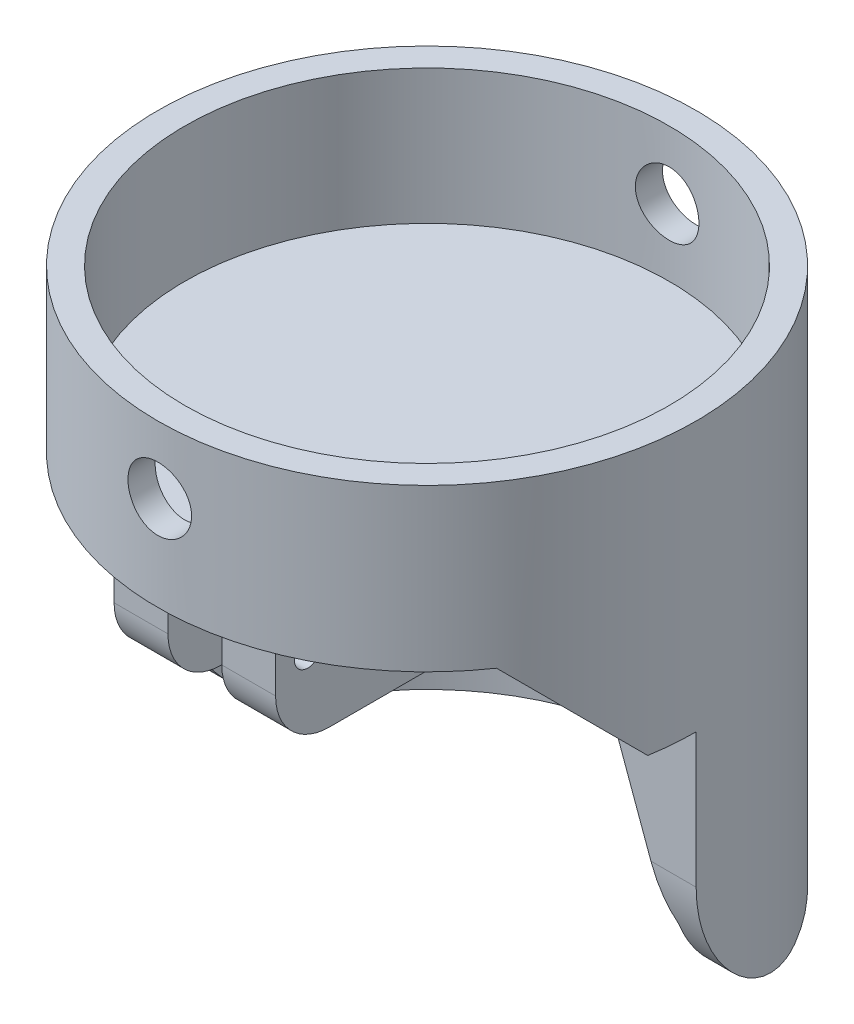
SolidWorks part; units mm, degrees
material "ABS"
ref_plane "Front Plane" through (0, 0, 0) normal (0, 0, 1) x (1, 0, 0)
ref_plane "Top Plane" through (0, 0, 0) normal (0, 1, 0) x (1, 0, 0)
ref_plane "Right Plane" through (0, 0, 0) normal (1, 0, 0) x (0, 0, -1)
sketch "Sketch2" plane through (0, 0, 0) normal (0, 1, 0) x (1, 0, 0)
  circle A0 centre (0, 0) radius 12.7
  dimension "D1" = 25.4
extrude "Boss-Extrude1" add sketch "Sketch2" along normal blind 12.7
sketch "Sketch3" plane through (0, 12.7, 0) normal (0, 1, 0) x (1, 0, 0)
  circle A0 centre (0, 0) radius 11.43
  dimension "D1" = 22.86
extrude "Cut-Extrude1" cut sketch "Sketch3" against normal blind 6.35
ref_plane "Plane1" through (0, 0, 12.7) normal (0, 0, 1) x (1, 0, 0)
sketch "Sketch4" plane through (0, 0, 12.7) normal (0, 0, 1) x (1, 0, 0)
  line L0 (0, 12.7) -> (0, 9.525)
  line L1 (12.7, 12.7) -> (-12.7, 12.7) construction
  circle A0 centre (0, 9.525) radius 1.5
  dimension "D2" = 3
  dimension "D1" = 3.175
extrude "Cut-Extrude2" cut sketch "Sketch4" against normal through all
sketch "Sketch5" plane through (0, 0, 0) normal (0, -1, 0) x (1, 0, 0)
  line L0 (-9.4733, 12.7) -> (9.4733, 12.7)
  line L1 (-9.4733, 12.7) -> (-9.4733, 8.4585)
  line L2 (-9.4733, 8.4585) -> (9.4733, 8.4585)
  line L3 (9.4733, 8.4585) -> (9.4733, 12.7)
  line L5 (-9.4733, 12.7) -> (9.4733, 12.7)
  line L10 (9.4733, 8.4585) -> (9.4733, 12.7)
  line L13 (-9.4733, 8.4585) -> (-11.846, 8.4585)
  line L14 (-9.4733, 8.4585) -> (-9.4733, 12.7)
  line L15 (-9.4733, 12.7) -> (-11.846, 12.7)
  circle A0 centre (0, 0) radius 12.7 construction
  point P2 (0, 12.7)
  dimension "D3" = 8.4585
extrude "Cut-Extrude3" cut sketch "Sketch5" against normal blind 5.08
sketch "Sketch6" plane through (0, 5.08, 0) normal (0, -1, 0) x (1, 0, 0)
  line L0 (-9.4733, 8.4585) -> (9.4733, 8.4585) construction
  line L1 (-6.35, 8.4585) -> (6.35, 8.4585)
  line L2 (-6.35, 8.4585) -> (-6.35, 10.9985)
  line L3 (-6.35, 10.9985) -> (6.35, 10.9985)
  line L4 (6.35, 8.4585) -> (6.35, 10.9985)
  line L5 (-3.7684, 10.9985) -> (-3.7684, 8.4585)
  line L6 (-1.2284, 10.9985) -> (-1.2284, 8.4585)
  line L7 (1.3116, 10.9985) -> (1.3116, 8.4585)
  line L8 (3.8516, 10.9985) -> (3.8516, 8.4585)
  arc A1 (9.4733, 8.4585) -> (-9.4733, 8.4585) centre (0, 0) ccw construction
  point P6 (0, 10.9985)
  dimension "D1" = 12.7
  dimension "D2" = 2.5816
  dimension "D3" = 2.54
  dimension "D4" = 2.54
  dimension "D5" = 2.54
sketch "Sketch7" plane through (0, 0, 0) normal (0, -1, 0) x (1, 0, 0)
  line L0 (-12.7, 0) -> (-11.43, 0)
  line L1 (11.43, 0) -> (12.7, 0)
  arc A0 (-12.7, 0) -> (12.7, 0) centre (0, 0) ccw
  arc A1 (-11.43, 0) -> (11.43, 0) centre (0, 0) ccw
  dimension "D1" = 22.86
extrude "Boss-Extrude3" add sketch "Sketch7" along normal blind 12.7
fillet "Fillet1" radius 6.35 2 edges at (12.065, -12.7, 0) (-12.065, -12.7, 0)
chamfer "Chamfer2" distance 3.175 angle 70 1 edges at (0, 0, -11.43) first distance on face at (0, 0, 1.0136)
sketch "Sketch9" plane through (0, 0, 0) normal (0, -1, 0) x (1, 0, 0)
  line L1 (-1.905, -1.27) -> (1.905, -1.27)
  line L2 (-1.905, -1.27) -> (-1.905, -7.62)
  line L3 (-1.905, -7.62) -> (1.905, -7.62)
  line L4 (1.905, -1.27) -> (1.905, -7.62)
  line L5 (-1.27, -3.81) -> (1.27, -3.81)
  line L6 (-1.27, -3.81) -> (-1.27, -5.08)
  line L7 (-1.27, -5.08) -> (1.27, -5.08)
  line L8 (1.27, -3.81) -> (1.27, -5.08)
  point P4 (0, -1.27)
  point P11 (0, -3.81)
  dimension "D1" = 6.35
  dimension "D2" = 3.81
  dimension "D3" = 1.27
  dimension "D4" = 2.54
  dimension "D5" = 2.54
  dimension "D6" = 2.54
extrude "Boss-Extrude4" add sketch "Sketch9" along normal blind 2.54
chamfer "Chamfer3" distance 1.27 angle 45 2 edges at (0, -2.54, -5.08) (0, -2.54, -3.81)
extrude "Boss-Extrude5" add sketch "Sketch6" along normal blind 5.08 contours L6 L3 L5 L1 | L8 L3 L7 L1
chamfer "Chamfer4" distance 6.35 angle 45 12 edges at (0.0416, 0, 8.4585) (0.0416, 5.08, 8.4585) (-1.2284, 2.54, 8.4585) (-3.7684, 2.54, 8.4585) (6.6625, 5.08, 8.4585) (6.6625, 0, 8.4585) (3.8516, 2.54, 8.4585) (1.3116, 2.54, 8.4585) (-6.6208, 0, 8.4585) (-6.6208, 5.08, 8.4585) (9.4733, 2.54, 8.4585) (-9.4733, 2.54, 8.4585)
sketch "Sketch11" plane through (-3.7684, 0, 0) normal (-1, 0, 0) x (0, 0, 1)
  line L0 (10.9985, 0) -> (10.9985, 5.08) construction
  line L2 (10.9985, 0) -> (2.1085, 0) construction
  circle A0 centre (9.4745, 3.556) radius 0.635
  dimension "D1" = 1.27
  dimension "D2" = 1.524
  dimension "D3" = 3.556
extrude "Cut-Extrude5" cut sketch "Sketch11" against normal through all
fillet "Fillet3" radius 2.54 2 edges at (-2.4984, 0, 10.9985) (2.5816, 0, 10.9985)
